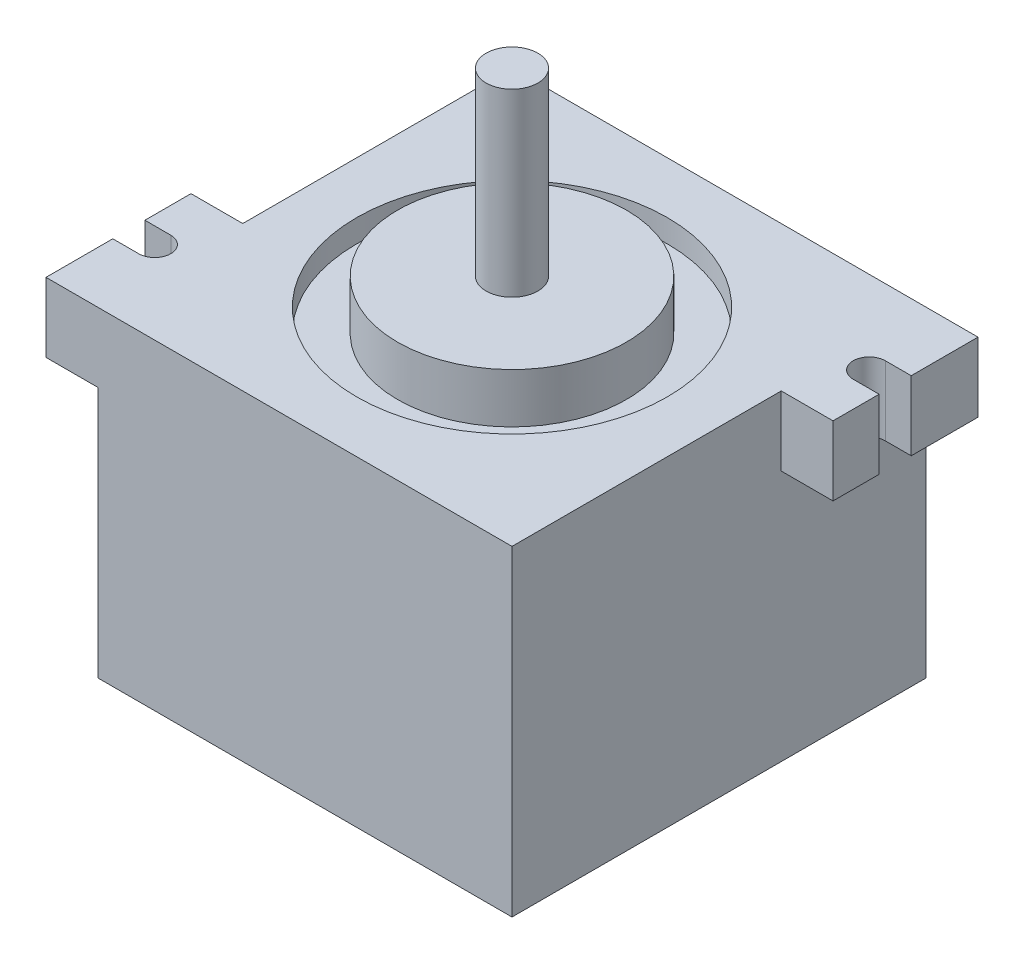
SolidWorks part; units mm, degrees
ref_plane "Front Plane" through (0, 0, 0) normal (0, 0, 1) x (1, 0, 0)
ref_plane "Top Plane" through (0, 0, 0) normal (0, 1, 0) x (1, 0, 0)
ref_plane "Right Plane" through (0, 0, 0) normal (1, 0, 0) x (0, 0, -1)
sketch "Sketch1" plane through (0, 0, 0) normal (0, 1, 0) x (1, 0, 0)
  line L1 (0, 0) -> (40, 0)
  line L2 (0, 0) -> (0, 40)
  line L3 (0, 40) -> (40, 40)
  line L4 (40, 0) -> (40, 40)
  dimension "D1" = 40
  dimension "D2" = 40
extrude "Boss-Extrude1" add sketch "Sketch1" along normal blind 31
sketch "Sketch2" plane through (0, 31, 0) normal (0, 1, 0) x (1, 0, 0)
  line L0 (20, 0) -> (20, 40) construction
  line L1 (0, 0) -> (40, 0) construction
  line L2 (40, 40) -> (0, 40) construction
  circle A0 centre (20, 20) radius 15
  dimension "D1" = 30
extrude "Cut-Extrude1" cut sketch "Sketch2" against normal blind 2.2
sketch "Sketch3" plane through (0, 28.8, 0) normal (0, 1, 0) x (1, 0, 0)
  circle A0 centre (20, 20) radius 11.05
  dimension "D1" = 22.1
extrude "Boss-Extrude2" add sketch "Sketch3" along normal blind 4.8
sketch "Sketch4" plane through (0, 33.6, 0) normal (0, 1, 0) x (1, 0, 0)
  circle A0 centre (20, 20) radius 2.5
  dimension "D1" = 5
extrude "Boss-Extrude3" add sketch "Sketch4" along normal blind 17.4
sketch "Sketch5" plane through (0, 31, 0) normal (0, 1, 0) x (1, 0, 0)
  line L0 (40, 32) -> (45, 32) construction
  line L1 (40, 40) -> (45, 40)
  line L2 (40, 40) -> (40, 26)
  line L3 (40, 26) -> (45, 26)
  line L4 (45, 40) -> (45, 33.55)
  line L5 (45, 30.45) -> (45, 26)
  line L6 (42.5, 33.55) -> (45, 33.55)
  line L8 (42.5, 30.45) -> (45, 30.45)
  arc A0 (42.5, 33.55) -> (42.5, 30.45) centre (42.5, 32) ccw
  point P9 (42.5, 32)
  dimension "D3" = 3.1
  dimension "D1" = 14
  dimension "D2" = 8
  dimension "D4" = 5
extrude "Boss-Extrude4" add sketch "Sketch5" against normal blind 6.7
ref_axis "Axis1" through (20, 51, -20) along (0, -1, 0)
pattern_circular "CirPattern1" count 2 over 360 about axis through (20, 51, -20) along (0, -1, 0) of "Boss-Extrude4"
sketch "Sketch6" plane through (0, 0, 0) normal (0, -1, 0) x (1, 0, 0)
  line L0 (40, -20) -> (0, -20) construction
  line L1 (40, 0) -> (40, -40) construction
  line L2 (0, -40) -> (0, 0) construction
  circle A0 centre (20, -20) radius 2.5
  dimension "D1" = 5
extrude "Boss-Extrude5" add sketch "Sketch6" along normal blind 0.5
